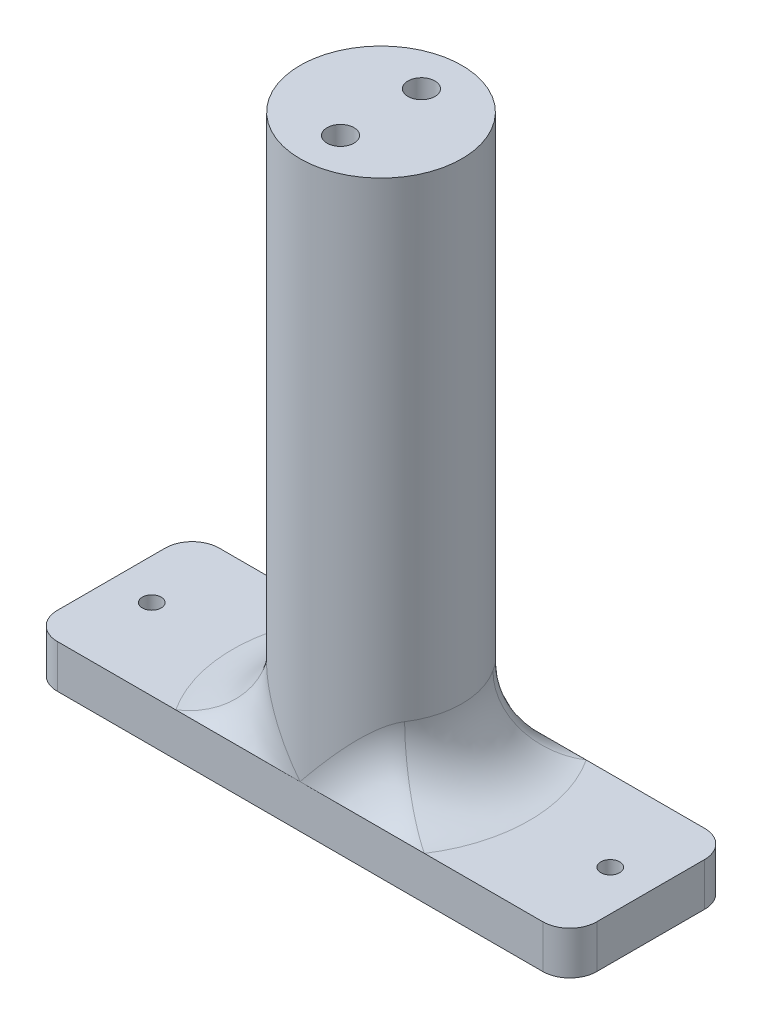
SolidWorks part; units mm, degrees
ref_plane "Front Plane" through (0, 0, 0) normal (0, 0, 1) x (1, 0, 0)
ref_plane "Top Plane" through (0, 0, 0) normal (0, 1, 0) x (1, 0, 0)
ref_plane "Right Plane" through (0, 0, 0) normal (1, 0, 0) x (0, 0, -1)
sketch "Sketch1" plane through (0, 0, 0) normal (0, 1, 0) x (1, 0, 0)
  line L0 (0, 3) -> (0, 0) construction
  line L1 (0, 0) -> (0, -3) construction
  circle A0 centre (0, 0) radius 6
  circle A1 centre (0, 3) radius 1
  circle A2 centre (0, -3) radius 1
  point P7 (0, 0)
  dimension "D1" = 12
  dimension "D2" = 2
  dimension "D3" = 2
  dimension "D4" = 6
  dimension "D5" = 3
extrude "Boss-Extrude1" add sketch "Sketch1" along normal blind 40
sketch "Sketch2" plane through (0, 0, 0) normal (0, -1, 0) x (1, 0, 0)
  line L0 (-17, 0) -> (0, 0) construction
  line L1 (-18, 6) -> (18, 6)
  line L2 (-20, 4) -> (-20, -4)
  line L3 (-18, -6) -> (18, -6)
  line L4 (20, 4) -> (20, -4)
  line L5 (-20, 6) -> (20, -6) construction
  line L6 (-20, -6) -> (20, 6) construction
  line L7 (0, 0) -> (17, 0) construction
  circle A0 centre (0, 0) radius 6 construction
  circle A1 centre (-17, 0) radius 0.7
  circle A2 centre (17, 0) radius 0.7
  circle A3 centre (-17, 0) radius 4.3 construction
  arc A4 (18, 6) -> (20, 4) centre (18, 4) cw
  arc A5 (18, -6) -> (20, -4) centre (18, -4) ccw
  arc A6 (-20, -4) -> (-18, -6) centre (-18, -4) ccw
  arc A7 (-18, 6) -> (-20, 4) centre (-18, 4) ccw
  point P4 (0, 0)
  dimension "D2" = 1.4
  dimension "D3" = 8.6
  dimension "D6" = 2
  dimension "D1" = 40
  dimension "D4" = 17
  dimension "D5" = 17
extrude "Boss-Extrude2" add sketch "Sketch2" along normal blind 3.2
fillet "Fillet1" radius 5 2 edges at (6, 0, 0) (-6, 0, 0)
